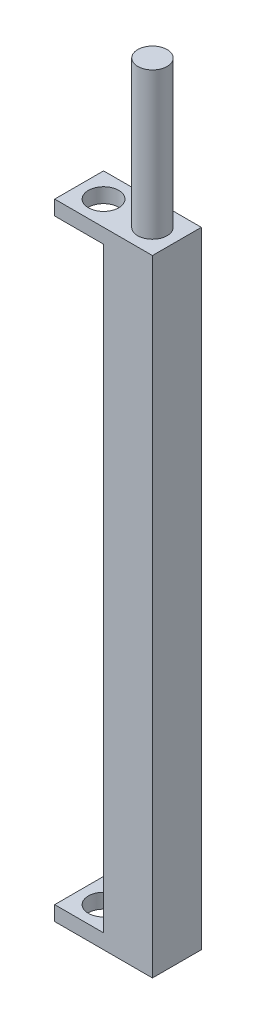
SolidWorks part; units mm, degrees
ref_plane "前视基准面" through (0, 0, 0) normal (0, 0, 1) x (1, 0, 0)
ref_plane "上视基准面" through (0, 0, 0) normal (0, 1, 0) x (1, 0, 0)
ref_plane "右视基准面" through (0, 0, 0) normal (1, 0, 0) x (0, 0, -1)
other "Configuration Table"
sketch "草图2" plane through (0, 0, 0) normal (0, 1, 0) x (1, 0, 0)
  line L1 (5, -2.5) -> (-5, -2.5)
  line L2 (5, -2.5) -> (5, 2.5)
  line L3 (5, 2.5) -> (-5, 2.5)
  line L4 (-5, -2.5) -> (-5, 2.5)
  line L5 (5, -2.5) -> (-5, 2.5) construction
  line L6 (5, 2.5) -> (-5, -2.5) construction
  circle A0 centre (2.5, 0) radius 1.55
  circle A1 centre (-2.5, 0) radius 1.55
  point P0 (0, 0)
  dimension "D3" = 3.1
  dimension "D4" = 3.1
  dimension "D1" = 10
  dimension "D2" = 2.5
  dimension "D5" = 2.5
  dimension "D6" = 5
extrude "凸台-拉伸1" add sketch "草图2" along normal blind 1.5 contours L3 L4 L1 L2
sketch "草图3" plane through (0, 0, 0) normal (0, -1, 0) x (1, 0, 0)
  line L0 (5, -2.5) -> (-5, -2.5) construction
  circle A0 centre (-2.5, 0) radius 1.55
  dimension "D3" = 3.1
  dimension "D1" = 2.5
  dimension "D2" = 2.5
extrude "切除-拉伸1" cut sketch "草图3" against normal blind 1.5
sketch "草图4" plane through (0, 0, 0) normal (0, -1, 0) x (1, 0, 0)
  line L0 (0, 2.5) -> (0, -2.5)
  line L1 (5, 2.5) -> (-5, 2.5) construction
  line L2 (5, -2.5) -> (-5, -2.5) construction
  line L3 (0, -2.5) -> (5, -2.5)
  line L4 (5, -2.5) -> (5, 2.5)
  line L5 (5, 2.5) -> (0, 2.5)
  dimension "D1" = 5
extrude "凸台-拉伸2" add sketch "草图4" along normal blind 61
sketch "草图5" plane through (0, -61, 0) normal (0, -1, 0) x (1, 0, 0)
  line L1 (5, 2.5) -> (-5, 2.5)
  line L2 (5, 2.5) -> (5, -2.5)
  line L3 (5, -2.5) -> (-5, -2.5)
  line L4 (-5, 2.5) -> (-5, -2.5)
extrude "凸台-拉伸3" add sketch "草图5" along normal blind 1.5
sketch "草图6" plane through (0, -62.5, 0) normal (0, -1, 0) x (1, 0, 0)
  line L0 (-5, 2.5) -> (-5, -2.5) construction
  circle A0 centre (-2.5, 0) radius 1.55
  dimension "D2" = 3.1
  dimension "D1" = 2.5
extrude "切除-拉伸2" cut sketch "草图6" against normal blind 1.5
sketch "草图7" plane through (0, 1.5, 0) normal (0, 1, 0) x (1, 0, 0)
  line L0 (5, -2.5) -> (5, 2.5) construction
  line L1 (5, -2.5) -> (-5, -2.5) construction
  circle A0 centre (2.5, 0) radius 1.5
  dimension "D1" = 3
  dimension "D2" = 2.5
  dimension "D3" = 2.5
extrude "凸台-拉伸4" add sketch "草图7" along normal blind 15 contours A0
sketch "草图11" plane through (0, -62.5, 0) normal (0, -1, 0) x (1, 0, 0)
  line L0 (-5, -2.5) -> (5, -2.5) construction
  line L1 (5, -2.5) -> (5, 2.5) construction
  circle A0 centre (2.5, 0) radius 1.55
  dimension "D3" = 3.1
  dimension "D1" = 2.5
  dimension "D2" = 2.5
extrude "切除-拉伸3" cut sketch "草图11" against normal blind 1
